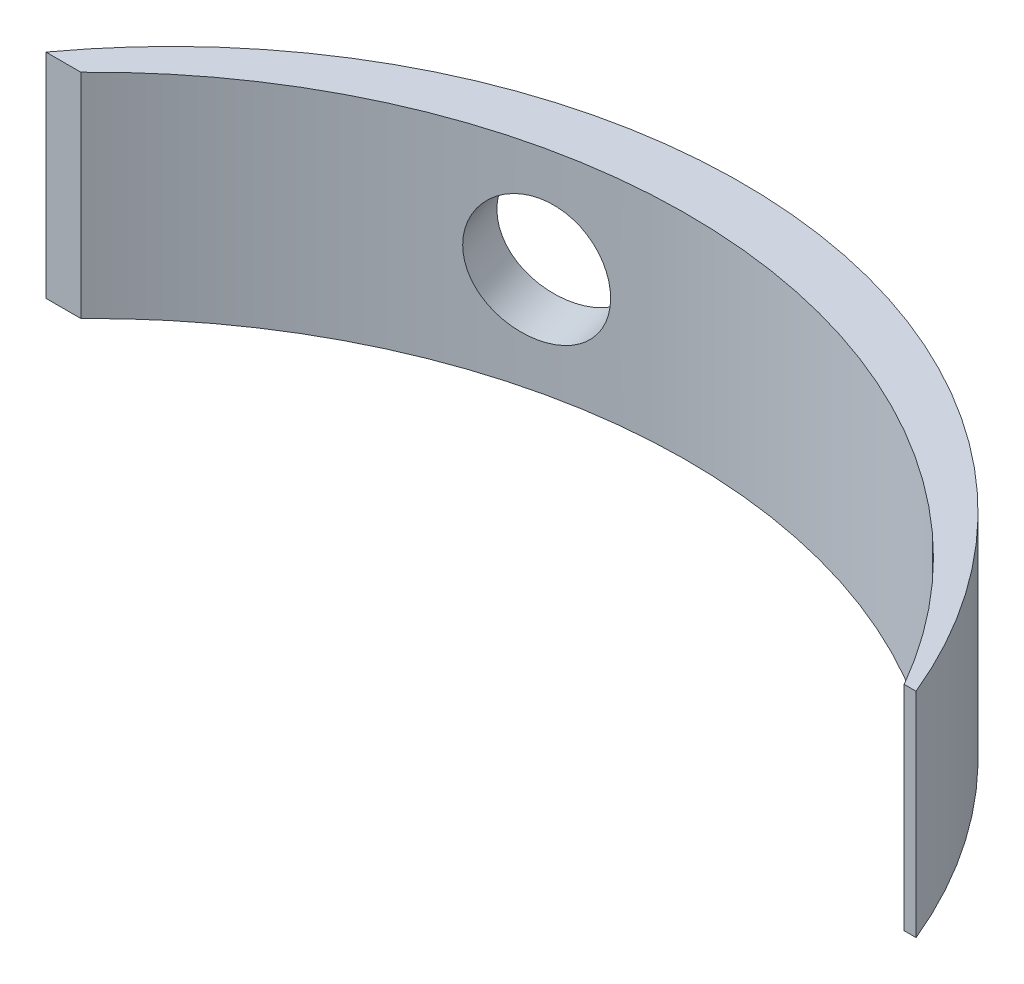
SolidWorks part; units mm, degrees
ref_plane "Front Plane" through (0, 0, 0) normal (0, 0, 1) x (1, 0, 0)
ref_plane "Top Plane" through (0, 0, 0) normal (0, 1, 0) x (1, 0, 0)
ref_plane "Right Plane" through (0, 0, 0) normal (1, 0, 0) x (0, 0, -1)
sketch "Sketch1" plane through (0, 0, 0) normal (0, 1, 0) x (1, 0, 0)
  line L0 (0, 0) -> (282.575, 0) construction
  line L1 (0, 0) -> (3.175, 0)
  line L2 (279.4, 0) -> (282.575, 0)
  arc A0 (0, 0) -> (282.575, 0) centre (141.2875, -58.184) cw
  arc A1 (3.175, 0) -> (279.4, 0) centre (141.2875, -79.1992) cw
  point P3 (141.2875, 94.615)
  point P8 (141.2875, 80.01)
  dimension "D2" = 94.615
  dimension "D1" = 282.575
  dimension "D3" = 276.225
  dimension "D4" = 80.01
  dimension "D5" = 3.175
extrude "Boss-Extrude1" add sketch "Sketch1" along normal blind 57.15
ref_plane "Plane3" through (-15.9662, 0, -55.6809) normal (-0.2756, 0, -0.9613) x (-0.9613, 0, 0.2756)
sketch "Sketch4" plane through (-15.9662, 0, -55.6809) normal (-0.2756, 0, -0.9613) x (-0.9613, 0, 0.2756)
  line L0 (0, 57.15) -> (-271.6285, 57.15) construction
  line L1 (0, 57.15) -> (0, 0) construction
  circle A0 centre (-122.428, 28.575) radius 16.51
  dimension "D2" = 122.428
  dimension "D1" = 28.575
extrude "Cut-Extrude1" cut sketch "Sketch4" against normal through all
sketch "Sketch5" plane through (0, 0, 0) normal (0, 1, 0) x (1, 0, 0)
  line L1 (0, 0) -> (49.6997, 0)
  line L2 (0, 0) -> (0, 31.75)
  line L3 (0, 31.75) -> (49.6997, 31.75)
  line L4 (49.6997, 0) -> (49.6997, 31.75)
  dimension "D1" = 31.75
extrude "Cut-Extrude2" cut sketch "Sketch5" along normal through all
ref_axis "Axis1" through (141.2875, 57.15, 58.184) along (0, -1, 0)
ref_plane "Plane4" through (146.5697, 0, 20.599) normal (0.9903, 0, 0.1392) x (0, -1, 0)
split "Split1" [suppressed] bodies to split 103
